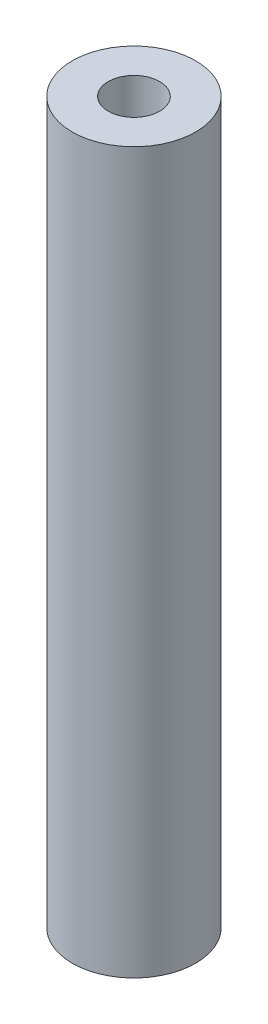
SolidWorks part; units mm, degrees
material "6061-T6 (SS)"
ref_plane "Front Plane" through (0, 0, 0) normal (0, 0, 1) x (1, 0, 0)
ref_plane "Top Plane" through (0, 0, 0) normal (0, 1, 0) x (1, 0, 0)
ref_plane "Right Plane" through (0, 0, 0) normal (1, 0, 0) x (0, 0, -1)
sketch "Sketch1" plane through (0, 0, 0) normal (0, 1, 0) x (1, 0, 0)
  circle A0 centre (0, 0) radius 3
  dimension "D1" = 6
extrude "Boss-Extrude1" add sketch "Sketch1" along normal blind 35
hole_wizard "Tap Drill for M3x0.5 Tap1" positions "Sketch2" profile "Sketch3" hole size "M3x0.5" standard "ANSI Metric" end condition up to next
sketch "Sketch2" plane through (0, 35, 0) normal (0, 1, 0) x (1, 0, 0)
  point P0 (0, 0)
sketch "Sketch3" plane through (0, 35, 0) normal (1, 0, 0) x (0, 0, 1)
  line L0 (0, 0) -> (0, 35)
  line L1 (0, 35) -> (1.25, 35)
  line L2 (1.25, 35) -> (1.25, 0)
  line L5 (1.25, 0) -> (0, 0)
  line L11 (0, -6.35) -> (0, 107.95) construction
  dimension "Thru Hole Dia." = 2.5
  dimension "Thru Hole Depth" = 35
